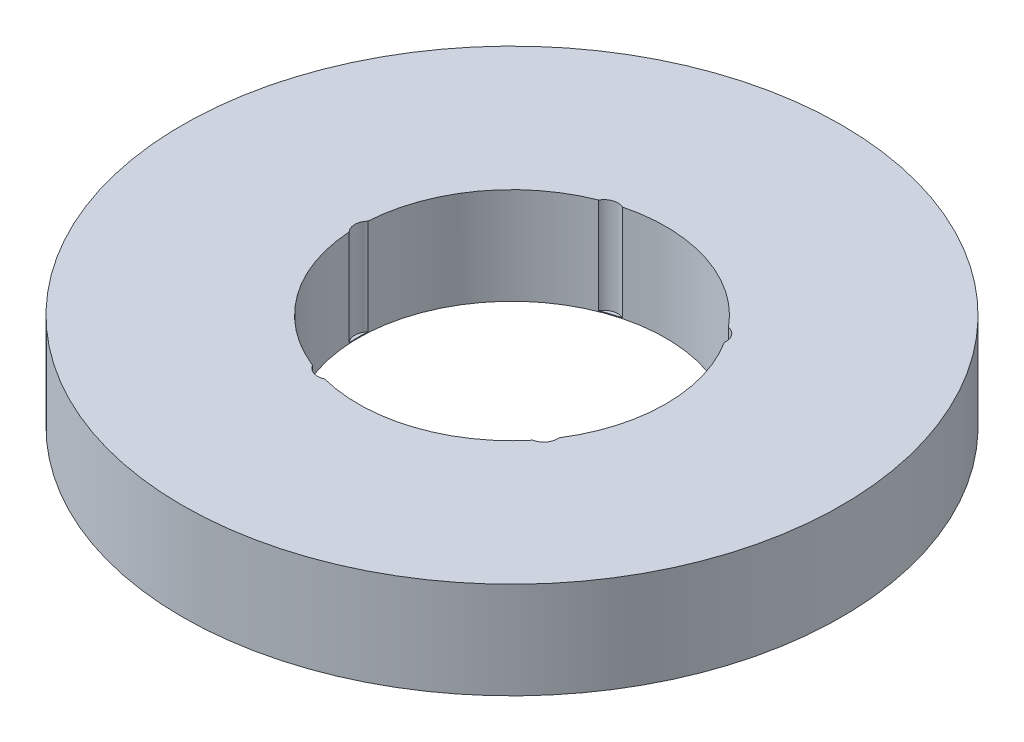
SolidWorks part; units mm, degrees
ref_plane "Front Plane" through (0, 0, 0) normal (0, 0, 1) x (1, 0, 0)
ref_plane "Top Plane" through (0, 0, 0) normal (0, 1, 0) x (1, 0, 0)
ref_plane "Right Plane" through (0, 0, 0) normal (1, 0, 0) x (0, 0, -1)
sketch "Sketch1" plane through (0, 0, 0) normal (0, 1, 0) x (1, 0, 0)
  circle A0 centre (0, 0) radius 75
  dimension "FLANGE_OD" = 150
extrude "Boss-Extrude1" add sketch "Sketch1" along normal blind 22
sketch "Sketch2" plane through (0, 0, 0) normal (0, 1, 0) x (1, 0, 0)
  circle A0 centre (0, 0) radius 35
  dimension "BORE_D" = 70
extrude "Cut-Extrude1" cut sketch "Sketch2" along normal through all
sketch "Sketch3" plane through (0, 22, 0) normal (0, 1, 0) x (1, 0, 0)
  circle A0 centre (0, 0) radius 32.5977 construction
  circle A1 centre (-32.5977, 0) radius 3.174
  dimension "BOLT_D" = 6.348
  dimension "BOLT_PCD" = 65.1955
extrude "Cut-Extrude2" cut sketch "Sketch3" against normal blind 21.8326
pattern_circular "CirPattern1" count 5 over 360 about axis through (0, 0, 0) along (0, 1, 0) of "Cut-Extrude2"
